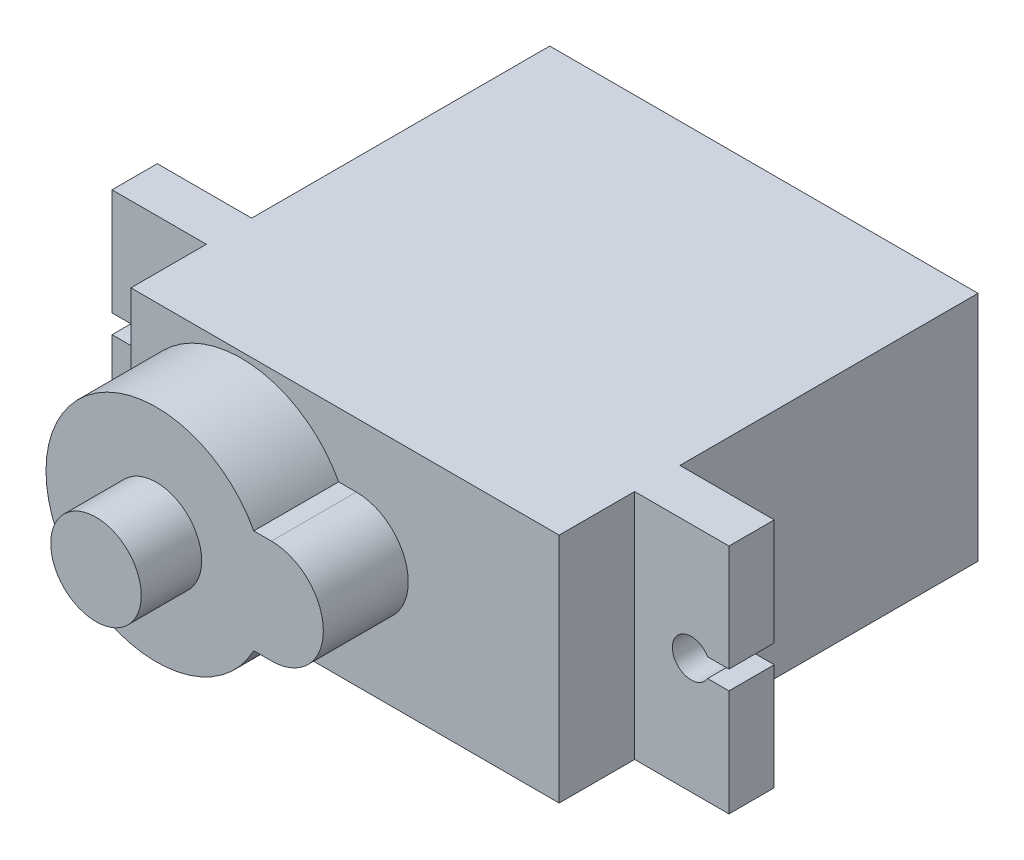
SolidWorks part; units mm, degrees
note: '?' marks a value the reader was unsure of.
ref_plane "Płaszczyzna przednia" through (0, 0, 0) normal (0, 0, 1) x (1, 0, 0)
ref_plane "Płaszczyzna górna" through (0, 0, 0) normal (0, 1, 0) x (1, 0, 0)
ref_plane "Płaszczyzna prawa" through (0, 0, 0) normal (1, 0, 0) x (0, 0, -1)
sketch "Szkic1" plane through (0, 0, 0) normal (0, 0, 1) x (1, 0, 0)
  line L1 (-22.9209, -0.2755) -> (-0.2209, -0.2755)
  line L2 (-22.9209, -0.2755) -> (-22.9209, -12.5755)
  line L3 (-22.9209, -12.5755) -> (-0.2209, -12.5755)
  line L4 (-0.2209, -0.2755) -> (-0.2209, -12.5755)
  dimension "D1" = 22.7
  dimension "D2" = 12.3
extrude "Dodanie-wyciągnięcie1" add sketch "Szkic1" along normal blind 22.2
sketch "Szkic2" plane through (-0.2209, 0, 0) normal (1, 0, 0) x (0, 0, -1)
  line L1 (-18.2, -12.5755) -> (-15.8, -12.5755)
  line L2 (-18.2, -12.5755) -> (-18.2, -0.2755)
  line L3 (-18.2, -0.2755) -> (-15.8, -0.2755)
  line L4 (-15.8, -12.5755) -> (-15.8, -0.2755)
  line L6 (-22.2, -12.5755) -> (0, -12.5755) construction
  line L7 (-22.2, -0.2755) -> (0, -0.2755) construction
  dimension "D1" = 2.4
  dimension "D2" = 4
extrude "Dodanie-wyciągnięcie2" add sketch "Szkic2" along normal blind 5 and the other way offset from surface (27.7 mm away) 5 other way up to face at (-22.9209, -6.4255, 11.1)
sketch "Szkic3" plane through (0, 0, 22.2) normal (0, 0, 1) x (1, 0, 0)
  line L0 (-10.9709, -9.1755) -> (-11.9076, -9.1755)
  line L1 (-10.9709, -3.6755) -> (-11.9076, -3.6755)
  line L3 (-0.2209, -6.4255) -> (-24.5009, -6.4255) construction
  line L4 (-22.9209, -0.2755) -> (-22.9209, -12.5755) construction
  line L5 (-0.2209, -12.5755) -> (-0.2209, -0.2755) construction
  line L7 (-22.9209, -0.2755) -> (-22.9209, -12.5755) construction
  arc A0 (-11.9076, -3.6755) -> (-11.9076, -9.1755) centre (-17.0709, -6.4255) ccw
  arc A1 (-10.9709, -9.1755) -> (-10.9709, -3.6755) centre (-10.9709, -6.4255) ccw
  point P15 (-8.2209, -6.4255)
  dimension "D1" = 14.7
  dimension "D2" = 5.85
  dimension "D3" = 2.75
extrude "Dodanie-wyciągnięcie3" add sketch "Szkic3" along normal blind 4.5
sketch "Szkic8" plane through (0, 0, 26.7) normal (0, 0, 1) x (1, 0, 0)
  circle A0 centre (-17.0709, -6.4255) radius 2.4
  point P0 (-17.0709, -6.4255)
extrude "Dodanie-wyciągnięcie4" add sketch "Szkic8" along normal blind 3.2
sketch "Szkic9" plane through (0, 0, 18.2) normal (0, 0, 1) x (1, 0, 0)
  line L0 (4.7791, -6.4255) -> (4.7791, -5.9255)
  line L2 (4.7791, -0.2755) -> (4.7791, -12.5755) construction
  line L3 (4.7791, -6.4255) -> (4.7791, -6.9255)
  line L4 (4.7791, -6.9255) -> (3.6451, -6.9255)
  line L5 (4.7791, -5.9255) -> (3.6451, -5.9255)
  arc A0 (3.6451, -5.9255) -> (3.6451, -6.9255) centre (2.7791, -6.4255) ccw
  dimension "D1" = 2
extrude "Wytnij-wyciągnięcie1" cut sketch "Szkic9" against normal up to surface (2.4 mm away) up to face at (2.2791, -6.4255, 15.8)
sketch "Szkic10" plane through (0, 0, 18.2) normal (0, 0, 1) x (1, 0, 0)
  line L0 (-27.9209, -5.9255) -> (-27.9209, -6.9255)
  line L2 (-27.9209, -5.9255) -> (-26.7869, -5.9255)
  line L3 (-27.9209, -6.9255) -> (-26.7869, -6.9255)
  line L4 (-27.9209, -12.5755) -> (-27.9209, -0.2755) construction
  arc A0 (-26.7869, -6.9255) -> (-26.7869, -5.9255) centre (-25.9209, -6.4255) ccw
  point P2 (-27.9209, -6.4255)
  point P10 (-27.9209, -6.4255)
extrude "Wytnij-wyciągnięcie2" cut sketch "Szkic10" against normal up to surface (2.4 mm away) up to face at (-25.4209, -6.4255, 15.8)
ref_axis "os serwa" through (-17.0709, -6.4255, 40.9917) along (0, 0, -1)?
sketch "Szkic11" plane through (-0.2209, 0, 0) normal (1, 0, 0) x (0, 0, -1)
  line L1 (-15.8, -0.2755) -> (0, -0.2755) construction
  line L2 (0, -12.5755) -> (0, -0.2755) construction
  line L9 (-40.9917, -6.4255) -> (12.3311, -6.4255) construction
  circle A4 centre (-4.75, -6.4255) radius 0.75
  circle A5 centre (-4.75, -4.9155) radius 0.75
  circle A6 centre (-4.75, -7.9355) radius 0.75
  dimension "D1" = 1.5
  dimension "D2" = 4.75
  dimension "D3" = 4.64
  dimension "D4" = 7.66
extrude "Dodanie-wyciągnięcie8" add sketch "Szkic11" against normal offset from surface (25.7 mm away) 3 up to face at (-22.9209, -6.4255, 7.9) offset beyond the face yes
